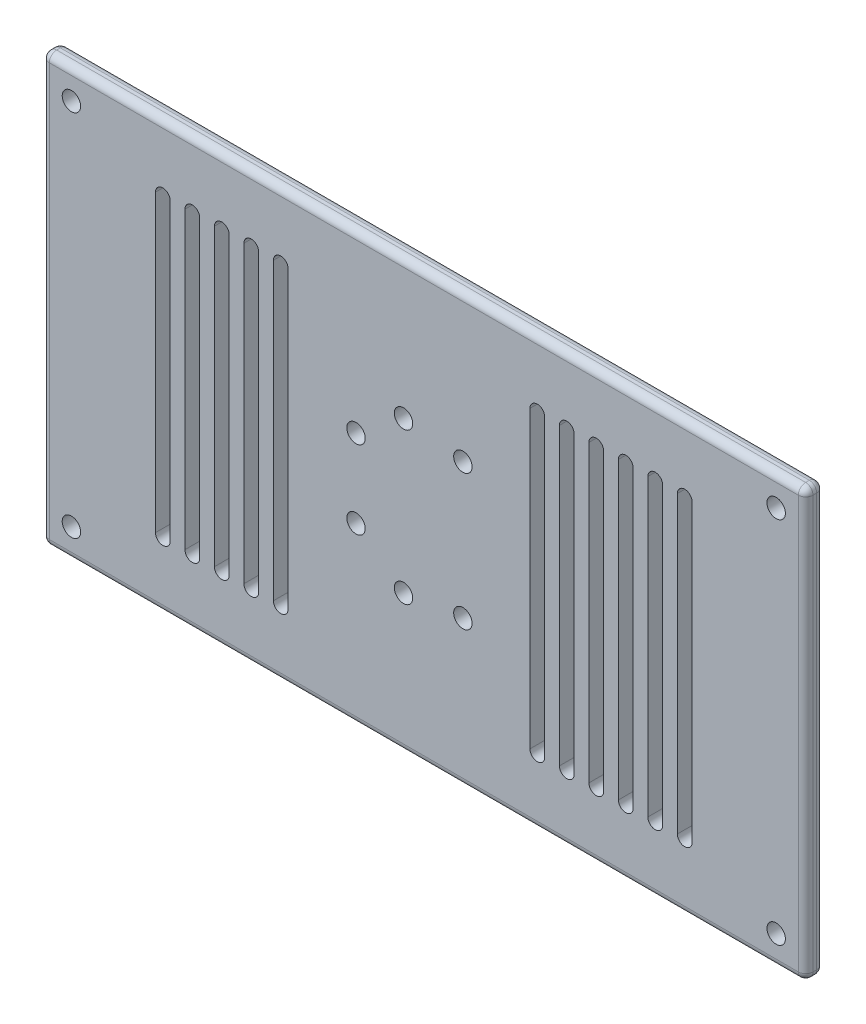
SolidWorks part; units mm, degrees
ref_plane "Plan de face" through (0, 0, 0) normal (0, 0, 1) x (1, 0, 0)
ref_plane "Plan de dessus" through (0, 0, 0) normal (0, 1, 0) x (1, 0, 0)
ref_plane "Plan de droite" through (0, 0, 0) normal (1, 0, 0) x (0, 0, -1)
sketch "Esquisse1" plane through (0, 0, 0) normal (0, 0, 1) x (1, 0, 0)
  line L1 (-51.8, 29) -> (51.8, 29)
  line L2 (-51.8, 29) -> (-51.8, -29)
  line L3 (-51.8, -29) -> (51.8, -29)
  line L4 (51.8, 29) -> (51.8, -29)
  line L5 (-51.8, 29) -> (51.8, -29) construction
  line L6 (-51.8, -29) -> (51.8, 29) construction
  point P0 (0, 0)
  point P5 (0, 0)
  point P6 (0, 0)
  point P13 (0, 0)
  point P16 (0, 0)
  dimension "D1" = 58
  dimension "D2" = 103.6
extrude "Boss.-Extru.1" add sketch "Esquisse1" along normal blind 2.5
sketch "Esquisse3" plane through (0, 0, 2.5) normal (0, 0, 1) x (1, 0, 0)
  line L0 (51.8, 29) -> (-51.8, 29) construction
  line L1 (-51.8, 29) -> (-51.8, -29) construction
  line L2 (-51.8, -29) -> (51.8, -29) construction
  line L3 (51.8, -29) -> (51.8, 29) construction
  circle A0 centre (-47.8, 25) radius 3
  circle A1 centre (47.8, 25) radius 3
  circle A2 centre (-47.8, -25) radius 3
  circle A3 centre (47.8, -25) radius 3
  point P17 (-47.8, 25)
  point P18 (-47.8, -25)
  point P19 (47.8, -25)
  point P20 (47.8, 25)
  dimension "D3" = 4
  dimension "D1" = 4
  dimension "D2" = 4
  dimension "D4" = 4
  dimension "D5" = 4
  dimension "D6" = 4
  dimension "D7" = 4
  dimension "D8" = 4
sketch "Esquisse17" plane through (0, 0, 2.5) normal (0, 0, 1) x (1, 0, 0)
  line L1 (-2.75, 10.25) -> (2.75, 10.25)
  line L2 (-2.75, 10.25) -> (-2.75, -10.25) construction
  line L3 (-2.75, -10.25) -> (2.75, -10.25)
  line L4 (2.75, 10.25) -> (2.75, -10.25)
  line L5 (-2.75, 10.25) -> (2.75, -10.25) construction
  line L6 (-2.75, -10.25) -> (2.75, 10.25) construction
  circle A0 centre (-2.75, 10.25) radius 3
  circle A1 centre (-2.75, -10.25) radius 3
  point P0 (0, 0)
  point P9 (-2.75, -10.25)
  point P10 (-2.75, 10.25)
  dimension "D1" = 20.5
  dimension "D2" = 5.5
fillet "Congé3" radius 1 12 edges at (-51.8, 0, 2.5) (0, -29, 2.5) (0, 29, 2.5) (51.8, 0, 2.5) (51.8, -29, 1.25) (51.8, 29, 1.25) (-51.8, 29, 1.25) (-51.8, -29, 1.25) (51.8, 0, 0) (0, 29, 0) (-51.8, 0, 0) (0, -29, 0)
sketch "Esquisse32" plane through (0, 0, 2.5) normal (0, 0, 1) x (1, 0, 0)
  line L1 (5.3033, 9.1924) -> (9.1924, 5.3033)
  line L2 (5.3033, 9.1924) -> (-9.1924, -5.3033)
  line L3 (-9.1924, -5.3033) -> (-5.3033, -9.1924)
  line L4 (9.1924, 5.3033) -> (-5.3033, -9.1924)
  line L5 (-2.75, 10.25) -> (2.75, -10.25) construction
  line L6 (-2.75, -10.25) -> (2.75, 10.25) construction
  circle A0 centre (5.3033, 9.1924) radius 3
  circle A1 centre (-9.1924, -5.3033) radius 3
  point P0 (0, 0)
extrude "Boss.-Extru.8" add sketch "Esquisse32" against normal blind 6.5 contours A1 | A0
sketch "Esquisse26" plane through (0, 0, 2.5) normal (0, 0, 1) x (1, 0, 0)
  line L1 (5.3033, -9.1924) -> (9.1924, -5.3033)
  line L2 (5.3033, -9.1924) -> (-9.1924, 5.3033)
  line L3 (-9.1924, 5.3033) -> (-5.3033, 9.1924)
  line L4 (9.1924, -5.3033) -> (-5.3033, 9.1924)
  line L5 (5.3033, -9.1924) -> (-5.3033, 9.1924) construction
  line L6 (-9.1924, 5.3033) -> (9.1924, -5.3033) construction
  circle A0 centre (-9.1924, 5.3033) radius 3
  circle A1 centre (5.3033, -9.1924) radius 3
  point P0 (0, 0)
  dimension "D1" = 5.5
  dimension "D2" = 20.5
extrude "Boss.-Extru.10" add sketch "Esquisse26" against normal blind 6.5 contours A1 | A0
extrude "Boss.-Extru.7" add sketch "Esquisse17" against normal blind 6.5 contours A0 | A1
hole_wizard "Trou pour taraudage pour trou taraudé M37" positions "Esquisse3D9" profile "Esquisse25" hole size "M3" standard "AS"
sketch3d "Esquisse3D9"
  point P0 (-2.75, -10.25, 2.5)
  point P3 (-2.75, 10.25, 2.5)
sketch "Esquisse25" plane through (-2.75, -10.25, 2.5) normal (1, 0, 0) x (0, -1, 0)
  line L0 (0, 0) -> (0, 5.7511)
  line L1 (0, 5.7511) -> (1.25, 5)
  line L2 (1.25, 5) -> (1.25, 0)
  line L5 (1.25, 0) -> (0, 0)
  line L10 (0, 5.7511) -> (-1.25, 5) construction
  line L11 (0, -6.35) -> (0, 107.95) construction
  dimension "Diamètre du perçage" = 2.5
  dimension "Profondeur du perçage" = 5
  dimension "Angle de pointe" = 118
hole_wizard "Trou pour taraudage pour trou taraudé M39" positions "Esquisse3D13" profile "Esquisse31" hole size "M3" standard "AS"
sketch3d "Esquisse3D13"
  point P0 (-9.1924, 5.3033, 2.5)
  point P3 (5.3033, -9.1924, 2.5)
sketch "Esquisse31" plane through (-9.1924, 5.3033, 2.5) normal (1, 0, 0) x (0, -1, 0)
  line L0 (0, 0) -> (0, 5.7511)
  line L1 (0, 5.7511) -> (1.25, 5)
  line L2 (1.25, 5) -> (1.25, 0)
  line L5 (1.25, 0) -> (0, 0)
  line L10 (0, 5.7511) -> (-1.25, 5) construction
  line L11 (0, -6.35) -> (0, 107.95) construction
  dimension "Diamètre du perçage" = 2.5
  dimension "Profondeur du perçage" = 5
  dimension "Angle de pointe" = 118
hole_wizard "Trou pour taraudage pour trou taraudé M310" positions "Esquisse3D14" profile "Esquisse33" hole size "M3" standard "AS"
sketch3d "Esquisse3D14"
  point P0 (5.3033, 9.1924, 2.5)
  point P3 (-9.1924, -5.3033, 2.5)
sketch "Esquisse33" plane through (5.3033, 9.1924, 2.5) normal (1, 0, 0) x (0, -1, 0)
  line L0 (0, 0) -> (0, 5.7511)
  line L1 (0, 5.7511) -> (1.25, 5)
  line L2 (1.25, 5) -> (1.25, 0)
  line L5 (1.25, 0) -> (0, 0)
  line L10 (0, 5.7511) -> (-1.25, 5) construction
  line L11 (0, -6.35) -> (0, 107.95) construction
  dimension "Diamètre du perçage" = 2.5
  dimension "Profondeur du perçage" = 5
  dimension "Angle de pointe" = 118
fillet "Congé5" radius 0.5 12 edges at (8.3033, -9.1924, -4) (0.25, -10.25, -4) (-6.1924, -5.3033, -4) (-6.1924, 5.3033, -4) (8.3033, 9.1924, -4) (0.25, 10.25, -4) (8.3033, 9.1924, 0) (0.25, 10.25, 0) (-6.1924, 5.3033, 0) (-6.1924, -5.3033, 0) (0.25, -10.25, 0) (8.3033, -9.1924, 0)
hole_wizard "Trou pour taraudage pour trou taraudé M311" positions "Esquisse3D15" profile "Esquisse34" hole size "M3" standard "AS"
sketch3d "Esquisse3D15"
  point P0 (47.8, 25, 2.5)
  point P3 (47.8, -25, 2.5)
  point P6 (-47.8, -25, 2.5)
  point P9 (-47.8, 25, 2.5)
sketch "Esquisse34" plane through (47.8, 25, 2.5) normal (1, 0, 0) x (0, -1, 0)
  line L0 (0, 0) -> (0, 5.7511)
  line L1 (0, 5.7511) -> (1.25, 5)
  line L2 (1.25, 5) -> (1.25, 0)
  line L5 (1.25, 0) -> (0, 0)
  line L10 (0, 5.7511) -> (-1.25, 5) construction
  line L11 (0, -6.35) -> (0, 107.95) construction
  dimension "Diamètre du perçage" = 2.5
  dimension "Profondeur du perçage" = 5
  dimension "Angle de pointe" = 118
sketch "Esquisse36" plane through (0, 0, 2.5) normal (0, 0, 1) x (1, 0, 0)
  line L0 (25.4, 0) -> (0, 0) construction
  line L1 (50.8, -28) -> (50.8, 28) construction
  line L2 (50.8, 0) -> (25.4, 0) construction
  line L4 (35.4, -20) -> (15.4, -20) construction
  line L5 (35.4, -20) -> (35.4, 20) construction
  line L6 (35.4, 20) -> (15.4, 20) construction
  line L7 (15.4, -20) -> (15.4, 20) construction
  line L8 (35.4, -20) -> (15.4, 20) construction
  line L9 (35.4, 20) -> (15.4, -20) construction
  line L10 (35.4, 20) -> (35.4, -20) construction
  line L11 (36.4, 20) -> (36.4, -20)
  line L12 (34.4, 20) -> (34.4, -20)
  arc A0 (36.4, 20) -> (34.4, 20) centre (35.4, 20) ccw
  arc A1 (34.4, -20) -> (36.4, -20) centre (35.4, -20) ccw
  point P0 (25.4, 0)
  point P2 (0, 0)
  point P8 (35.4, 0)
  dimension "D1" = 20
  dimension "D2" = 40
extrude "Enlèv. mat.-Extru.2" cut sketch "Esquisse36" against normal through all
pattern_linear "Répétition linéaire1" count 6 spacing 4 along (-1, 0, 0) of "Enlèv. mat.-Extru.2"
sketch "Esquisse37" plane through (0, 0, 2.5) normal (0, 0, 1) x (1, 0, 0)
  line L0 (0, 0) -> (-50.8, 0) construction
  line L1 (-50.8, 28) -> (-50.8, -28) construction
  line L2 (-35.4, 20) -> (-35.4, -20) construction
  line L3 (-15.4, 20) -> (-35.4, 20) construction
  line L4 (-15.4, 20) -> (-15.4, -20) construction
  line L5 (-15.4, -20) -> (-35.4, -20) construction
  line L6 (-35.4, 20) -> (-35.4, -20) construction
  line L7 (-15.4, 20) -> (-35.4, -20) construction
  line L8 (-15.4, -20) -> (-35.4, 20) construction
  line L9 (-34.4, 20) -> (-34.4, -20)
  line L10 (-36.4, 20) -> (-36.4, -20)
  arc A0 (-34.4, 20) -> (-36.4, 20) centre (-35.4, 20) ccw
  arc A1 (-36.4, -20) -> (-34.4, -20) centre (-35.4, -20) ccw
  point P5 (-25.4, 0)
  point P11 (-35.4, 0)
  dimension "D1" = 40
  dimension "D2" = 20
extrude "Enlèv. mat.-Extru.3" cut sketch "Esquisse37" against normal through all
pattern_linear "Répétition linéaire2" count 5 spacing 4 along (1, 0, 0) of "Enlèv. mat.-Extru.3"
